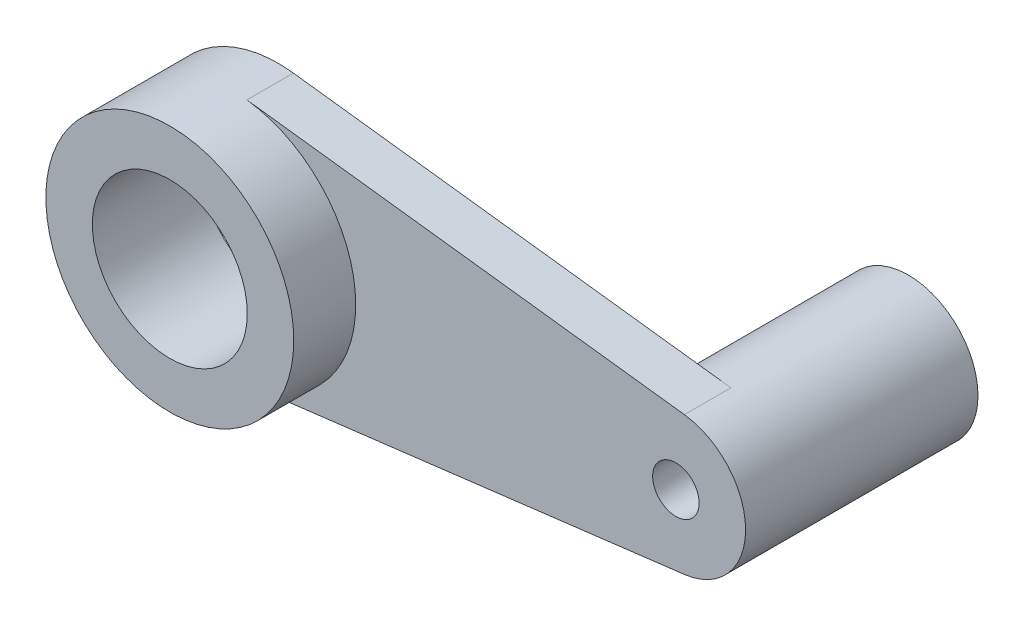
SolidWorks part; units mm, degrees
ref_plane "Front Plane" through (0, 0, 0) normal (0, 0, 1) x (1, 0, 0)
ref_plane "Top Plane" through (0, 0, 0) normal (0, 1, 0) x (1, 0, 0)
ref_plane "Right Plane" through (0, 0, 0) normal (1, 0, 0) x (0, 0, -1)
sketch "Sketch3" plane through (0, 0, 0) normal (0, 0, 1) x (1, 0, 0)
  line L0 (58.4304, 8.9327) -> (1.9535, 15.8803)
  line L1 (58.4304, -8.9327) -> (1.9535, -15.8803)
  circle A0 centre (0, 0) radius 10
  circle A1 centre (0, 0) radius 16
  circle A2 centre (57.3316, 0) radius 3
  circle A3 centre (57.3316, 0) radius 9
extrude "Boss-Extrude4" add sketch "Sketch3" along normal blind 14 contours A1 A0 region at (11.6455, 10.3007, 0)
extrude "Boss-Extrude5" add sketch "Sketch3<3>" along normal blind 6 contours A3 A1 region at (30.6092, 0, 0)
sketch "Sketch3<3>" plane through (0, 0, 0) normal (0, 0, 1) x (1, 0, 0) same geometry as "Sketch3"
extrude "Boss-Extrude6" add sketch "Sketch3<4>" along normal blind 6 and the other way blind 24 contours A3 A2 region at (63.8822, 5.7942, 0)
sketch "Sketch3<4>" plane through (0, 0, 0) normal (0, 0, 1) x (1, 0, 0) same geometry as "Sketch3"
